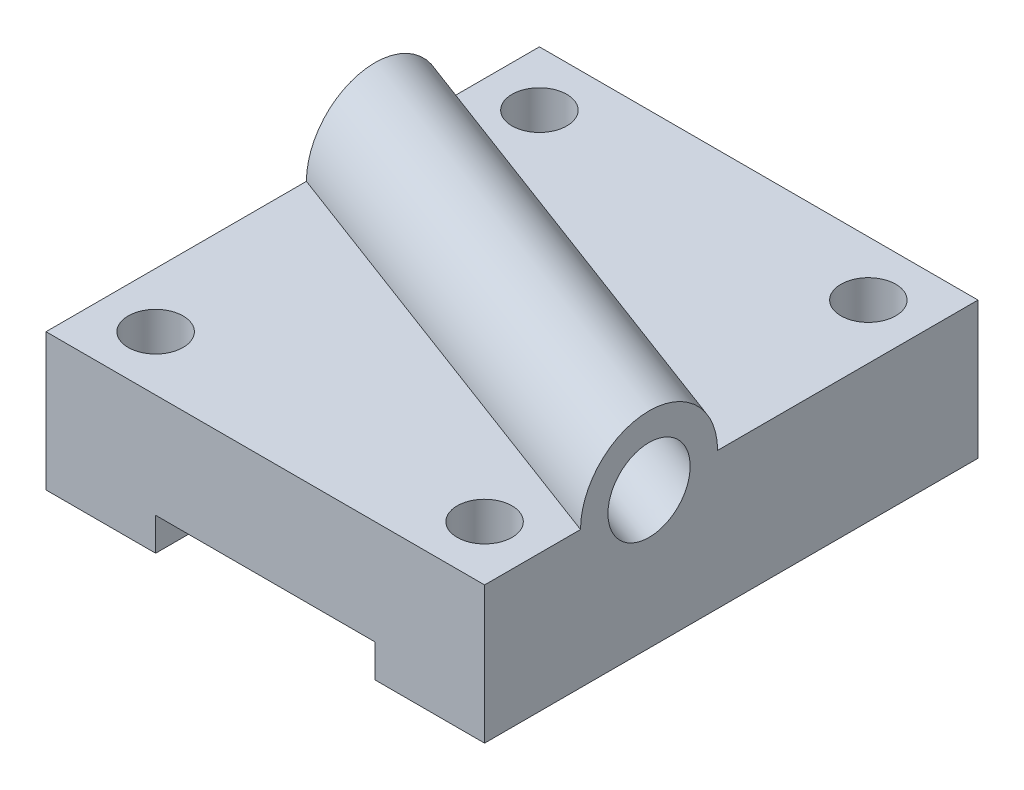
SolidWorks part; units mm, degrees
ref_plane "Alzado" through (0, 0, 0) normal (0, 0, 1) x (1, 0, 0)
ref_plane "Planta" through (0, 0, 0) normal (0, 1, 0) x (1, 0, 0)
ref_plane "Vista lateral" through (0, 0, 0) normal (1, 0, 0) x (0, 0, -1)
sketch "Croquis1" plane through (0, 0, 0) normal (0, 0, 1) x (1, 0, 0)
  line L0 (-20, 0) -> (20, 0) construction
  line L1 (-20, 0) -> (-20, 6)
  line L2 (-20, 6) -> (20, 6)
  line L3 (20, 6) -> (20, 0)
  line L4 (20, 0) -> (40, 0)
  line L5 (40, 0) -> (40, 25)
  line L6 (40, 25) -> (-40, 25)
  line L7 (-40, 25) -> (-40, 0)
  line L8 (-40, 0) -> (-20, 0)
  point P3 (0, 25)
  point P4 (0, 0)
  dimension "D1" = 6
  dimension "D2" = 40
  dimension "D3" = 25
  dimension "D4" = 80
extrude "Saliente-Extruir1" add sketch "Croquis1" against normal blind 90
ref_plane "Plano1" through (40, 0, 0) normal (1, 0, 0) x (0, 0, -1)
sketch "Croquis4" plane through (40, 0, 0) normal (1, 0, 0) x (0, 0, -1)
  line L0 (90, 25) -> (0, 25) construction
  line L1 (17.5, 25) -> (42.5, 25) construction
  line L2 (17.5, 25) -> (42.5, 25)
  arc A1 (42.5, 25) -> (17.5, 25) centre (30, 25) ccw
  dimension "D3" = 12.5
  dimension "D1" = 30
ref_plane "Plano4" through (-40, 0, 0) normal (-1, 0, 0) x (0, 0, 1)
sketch "Croquis7" plane through (-40, 0, 0) normal (-1, 0, 0) x (0, 0, 1)
  line L0 (-90, 25) -> (0, 25) construction
  line L1 (-72.5, 25) -> (-47.5, 25)
  arc A0 (-47.5, 25) -> (-72.5, 25) centre (-60, 25) ccw
  dimension "D1" = 12.5
  dimension "D2" = 30
loft "Recubrir5" add profiles "Croquis7", "Croquis4" connector at (-40, 25, -72.5) connector at (40, 25, -42.5)
sketch "Croquis11" plane through (-40, 0, 0) normal (-1, 0, 0) x (0, 0, 1)
  circle A0 centre (-60, 25) radius 7.5
  dimension "D1" = 15
  dimension "D2" = 30
  dimension "D3" = 25
sketch "Croquis12" plane through (40, 0, 0) normal (1, 0, 0) x (0, 0, -1)
  circle A0 centre (30, 25) radius 7.5
  dimension "D1" = 15
  dimension "D2" = 30
  dimension "D3" = 25
loft "Cortar-Recubrir9" cut profiles "Croquis12", "Croquis11" connector at (40, 32.4992, -30.1118) connector at (-40, 32.4078, -58.8275)
ref_plane "Plano5" through (0, 25, 0) normal (0, 1, 0) x (1, 0, 0)
sketch "Croquis13" plane through (0, 25, 0) normal (0, 1, 0) x (1, 0, 0)
  line L0 (40, 90) -> (-40, 90) construction
  line L1 (-40, 24.5361) -> (-40, -24.5361) construction
  line L2 (0, 90) -> (0, 0) construction
  line L3 (-40, 45) -> (40, 45) construction
  line L4 (40, -24.5361) -> (40, 24.5361) construction
  circle A0 centre (-30, 80) radius 5
  circle A4 centre (30, 80) radius 5
  circle A5 centre (30, 10) radius 5
  circle A6 centre (-30, 10) radius 5
  point P20 (0, 45)
  dimension "D1" = 10
  dimension "D2" = 10
  dimension "D3" = 10
extrude "Cortar-Extruir1" cut sketch "Croquis13" against normal up to next
